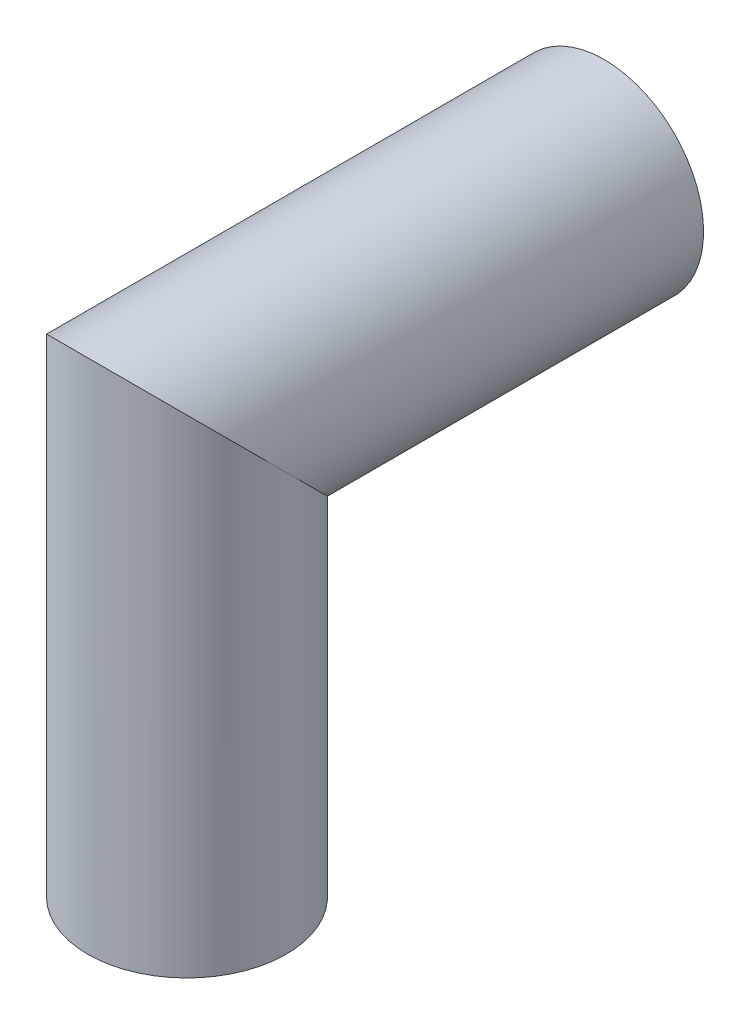
SolidWorks part; units mm, degrees
material "Silicon Rubber"
ref_plane "Front Plane" through (0, 0, 0) normal (0, 0, 1) x (1, 0, 0)
ref_plane "Top Plane" through (0, 0, 0) normal (0, 1, 0) x (1, 0, 0)
ref_plane "Right Plane" through (0, 0, 0) normal (1, 0, 0) x (0, 0, -1)
sketch "Sketch2" plane through (0, 0, 0) normal (0, 1, 0) x (1, 0, 0)
  line L0 (0, 2.5) -> (0, 8) construction
  line L1 (-17.5, 0) -> (17.5, 0) construction
  circle A0 centre (0, 0) radius 17.5 construction
  circle A1 centre (0, 0) radius 2.5 construction
  circle A2 centre (0, 8) radius 3.175
  circle A3 centre (0, 8) radius 4.7625
  circle A4 centre (0, -8) radius 3.175 construction
  circle A5 centre (0, -8) radius 4.7625 construction
  dimension "D1" = 35
  dimension "D2" = 5
  dimension "D4" = 6.35
  dimension "D5" = 9.525
  dimension "D3" = 5.5
sketch "Sketch4" plane through (0, 0, 0) normal (1, 0, 0) x (0, 0, -1)
  line L0 (8, 0) -> (8, 20)
  line L1 (8, 20) -> (28, 20)
  dimension "D1" = 20
  dimension "D2" = 20
sweep "Sweep2" add profiles "Sketch2" path "Sketch4"
